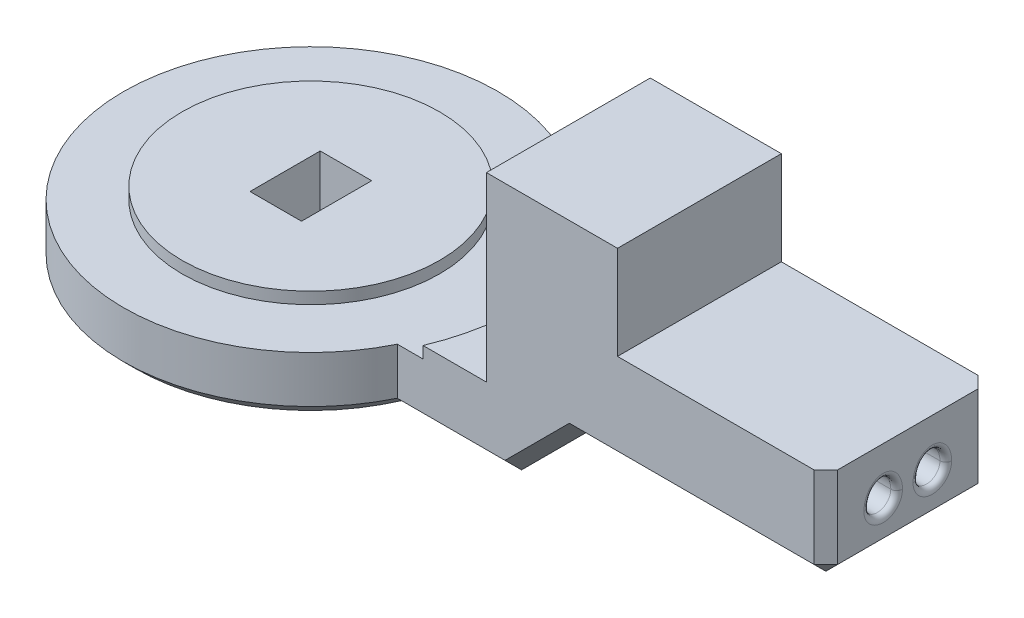
SolidWorks part; units mm, degrees
ref_plane "Front Plane" through (0, 0, 0) normal (0, 0, 1) x (1, 0, 0)
ref_plane "Top Plane" through (0, 0, 0) normal (0, 1, 0) x (1, 0, 0)
ref_plane "Right Plane" through (0, 0, 0) normal (1, 0, 0) x (0, 0, -1)
sketch "Sketch1" plane through (0, 0, 0) normal (0, 1, 0) x (1, 0, 0)
  line L0 (-1.1, 1.0198) -> (-1.1, -1.0198)
  line L1 (1.1, 1.0198) -> (1.1, -1.0198)
  line L2 (-998.0463, -3.5) -> (49001.9537, -3.5) construction
  line L3 (-998.5569, 3.5) -> (49001.4431, 3.5) construction
  line L4 (21.6, -1002.9744) -> (21.6, 48997.0256) construction
  line L5 (7.1937, 3.5) -> (21.6, 3.5)
  line L6 (21.6, 3.5) -> (21.6, -3.5)
  line L7 (21.6, -3.5) -> (7.1937, -3.5)
  line L8 (0.887, 1.2096) -> (1.1, 1.5) construction
  line L9 (-1.1, 1.5) -> (1.1, 1.5)
  line L10 (-1.1, 1.5) -> (-1.1, -1.5)
  line L11 (-1.1, -1.5) -> (1.1, -1.5)
  line L12 (1.1, 1.5) -> (1.1, -1.5)
  line L13 (-0.887, 1.2096) -> (1.1, -1.5) construction
  line L14 (-1.1, -1.5) -> (0.887, 1.2096) construction
  line L15 (-1.1, 1.5) -> (-0.887, 1.2096) construction
  arc A0 (-1.1, -1.0198) -> (-0.887, -1.2096) centre (0, 0) ccw construction
  arc A1 (-1.1, 1.0198) -> (-1.1, -1.0198) centre (0, 0) ccw construction
  arc A2 (1.1, -1.0198) -> (1.1, 1.0198) centre (0, 0) ccw construction
  arc A3 (-0.887, 1.2096) -> (-1.1, 1.0198) centre (0, 0) ccw construction
  arc A4 (7.1937, 3.5) -> (7.1937, -3.5) centre (0, 0) ccw
  arc A5 (7.1937, -3.5) -> (7.1937, 3.5) centre (0, 0) ccw construction
  arc A6 (-0.887, -1.2096) -> (0, -1.5) centre (0, 0) ccw construction
  arc A7 (0.887, -1.2096) -> (1.1, -1.0198) centre (0, 0) ccw construction
  arc A8 (0, -1.5) -> (0.887, -1.2096) centre (0, 0) ccw construction
  arc A9 (1.1, 1.0198) -> (0.887, 1.2096) centre (0, 0) ccw construction
  arc A10 (0.887, 1.2096) -> (0, 1.5) centre (0, 0) ccw construction
  arc A11 (0, 1.5) -> (-0.887, 1.2096) centre (0, 0) ccw construction
  dimension "D1" = 3
  dimension "D4" = 16
  dimension "D2" = 1.1
  dimension "D3" = 1.1
  dimension "D5" = 3.5
  dimension "D6" = 3.5
  dimension "D7" = 21.6
extrude "Boss-Extrude1" add sketch "Sketch1" against normal blind 3 contours L5 A4 L7 L6 L9 L12 L1 L11 L10 L0 region at (4.8825, 0, 0)
sketch "Sketch2" plane through (0, 0, 0) normal (0, 1, 0) x (1, 0, 0)
  circle A0 centre (0, 0) radius 9
  circle A1 centre (0, 0) radius 5.5
  dimension "D1" = 18
  dimension "D2" = 3.5
extrude "Cut-Extrude1" cut sketch "Sketch2" against normal blind 0.5
sketch "Sketch3" plane through (0, 0, 0) normal (0, 1, 0) x (1, 0, 0)
  line L1 (21.6, 3.5) -> (11, 3.5)
  line L2 (21.6, 3.5) -> (21.6, -3.5)
  line L3 (21.6, -3.5) -> (11, -3.5)
  line L4 (11, 3.5) -> (11, -3.5)
  line L5 (21.6, -3.5) -> (8.2916, -3.5) construction
  dimension "D1" = 11
extrude "Boss-Extrude2" add sketch "Sketch3" along normal blind 3.75
sketch "Sketch5" plane through (0, -3, 0) normal (0, -1, 0) x (1, 0, 0)
  line L0 (21.6, -3.5) -> (25.5, -3.5)
  line L1 (21.6, 3.5) -> (25.5, 3.5)
  line L2 (25.5, 3.5) -> (25.5, -3.5)
  line L3 (21.6, 3.5) -> (21.6, -3.5)
  dimension "D1" = 3.9
extrude "Boss-Extrude3" add sketch "Sketch5" against normal up to vertex (6.75 mm away) up to point (21.6, 3.75, 3.5)
sketch "Sketch6" plane through (11, 0, 0) normal (-1, 0, 0) x (0, 0, 1)
  line L0 (6.5, 1.65) -> (-6.5, 1.65) construction
  line L4 (-3.5, 0) -> (3.5, 0) construction
  arc A0 (0.475, 1.65) -> (1.625, 1.65) centre (1.05, 1.65) ccw
  arc A1 (-1.625, 1.65) -> (-0.475, 1.65) centre (-1.05, 1.65) ccw
  arc A2 (1.625, 1.65) -> (0.475, 1.65) centre (1.05, 1.65) ccw construction
  arc A3 (-0.475, 1.65) -> (-1.625, 1.65) centre (-1.05, 1.65) ccw construction
  ellipse E0 centre (-1.05, 1.65) end of major axis (-1.05, 2.4) minor radius 0.575 (-0.475, 1.65) -> (-1.625, 1.65) ccw
  ellipse E1 centre (1.05, 1.65) end of major axis (1.05, 2.4) minor radius 0.575 (1.625, 1.65) -> (0.475, 1.65) ccw
  ellipse E2 centre (-1.05, 1.65) end of major axis (-1.05, 2.4) minor radius 0.575 (-1.625, 1.65) -> (-0.475, 1.65) ccw construction
  ellipse E3 centre (1.05, 1.65) end of major axis (1.05, 2.4) minor radius 0.575 (0.475, 1.65) -> (1.625, 1.65) ccw construction
  dimension "D1" = 1.15
  dimension "D2" = 1.15
  dimension "D3" = 2.1
  dimension "D4" = 1.05
  dimension "D5" = 1.65
  dimension "D6" = 0.75
  dimension "D7" = 0.75
extrude "Cut-Extrude3" cut sketch "Sketch6" against normal through all
fillet "Fillet2" radius 0.25 8 edges at (11, 1.075, -1.05) (25.5, 1.075, -1.05) (11, 1.075, 1.05) (25.5, 1.075, 1.05) (25.5, 2.4, -1.05) (11, 2.4, -1.05) (25.5, 2.4, 1.05) (11, 2.4, 1.05)
sketch "Sketch7" plane through (0, 3.75, 0) normal (0, 1, 0) x (1, 0, 0)
  line L0 (11, -3.5) -> (25.5, -3.5) construction
  line L1 (11, 3.5) -> (16.6, 3.5)
  line L2 (11, 3.5) -> (11, -3.5)
  line L3 (11, -3.5) -> (16.6, -3.5)
  line L4 (16.6, 3.5) -> (16.6, -3.5)
  dimension "D1" = 5.6
extrude "Boss-Extrude4" add sketch "Sketch7" along normal blind 4
sketch "Sketch9" plane through (0, -3, 0) normal (0, -1, 0) x (1, 0, 0)
  line L0 (7.1937, -3.5) -> (25.5, -3.5) construction
  line L1 (25.5, 3.5) -> (12, 3.5)
  line L2 (25.5, 3.5) -> (25.5, -3.5)
  line L3 (25.5, -3.5) -> (12, -3.5)
  line L4 (12, 3.5) -> (12, -3.5)
  dimension "D1" = 12
extrude "Cut-Extrude5" cut sketch "Sketch9" against normal blind 2.75
chamfer "Chamfer2" distance 2.75 angle 45 1 edges at (12, -0.25, 0)
chamfer "Chamfer1" distance 0.5 14 edges at (25.5, 1.75, -3.5) (25.5, 1.75, 3.5) (-8, -3, 0) (9.5969, -3, -3.5) (9.5969, -3, 3.5) (1.1, -3, 0) (0, -3, -1.5) (-1.1, -3, 0) (0, -3, 1.5) (13.375, -1.625, -3.5) (20.125, -0.25, -3.5) (25.5, -0.25, 0) (13.375, -1.625, 3.5) (20.125, -0.25, 3.5)
